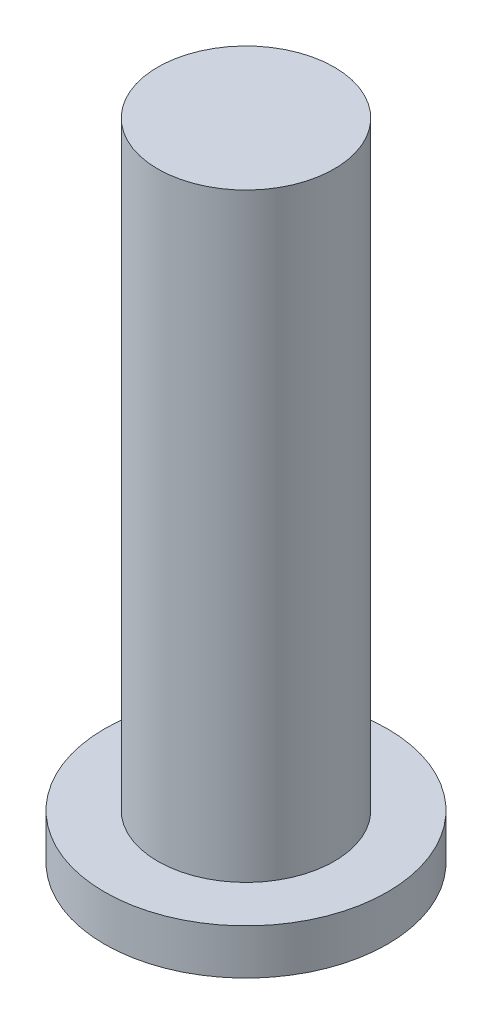
SolidWorks part; units mm, degrees
ref_plane "Front Plane" through (0, 0, 0) normal (0, 0, 1) x (1, 0, 0)
ref_plane "Top Plane" through (0, 0, 0) normal (0, 1, 0) x (1, 0, 0)
ref_plane "Right Plane" through (0, 0, 0) normal (1, 0, 0) x (0, 0, -1)
sketch "Sketch1" plane through (0, 0, 0) normal (0, 1, 0) x (1, 0, 0)
  circle A0 centre (0, 0) radius 4.953
  circle A1 centre (0, 0) radius 7.9375
  dimension "D1" = 9.906
  dimension "D2" = 15.875
extrude "Boss-Extrude1" add sketch "Sketch1" along normal blind 33.655 contours A0 region at (0, 0, 0)
extrude "Boss-Extrude2" add sketch "Sketch1<3>" against normal blind 2.54 contours A0 | A1 A0 region at (0, 0, 0) region at (-7.713, 0, 0)
sketch "Sketch1<3>" plane through (0, 0, 0) normal (0, 1, 0) x (1, 0, 0) same geometry as "Sketch1"
